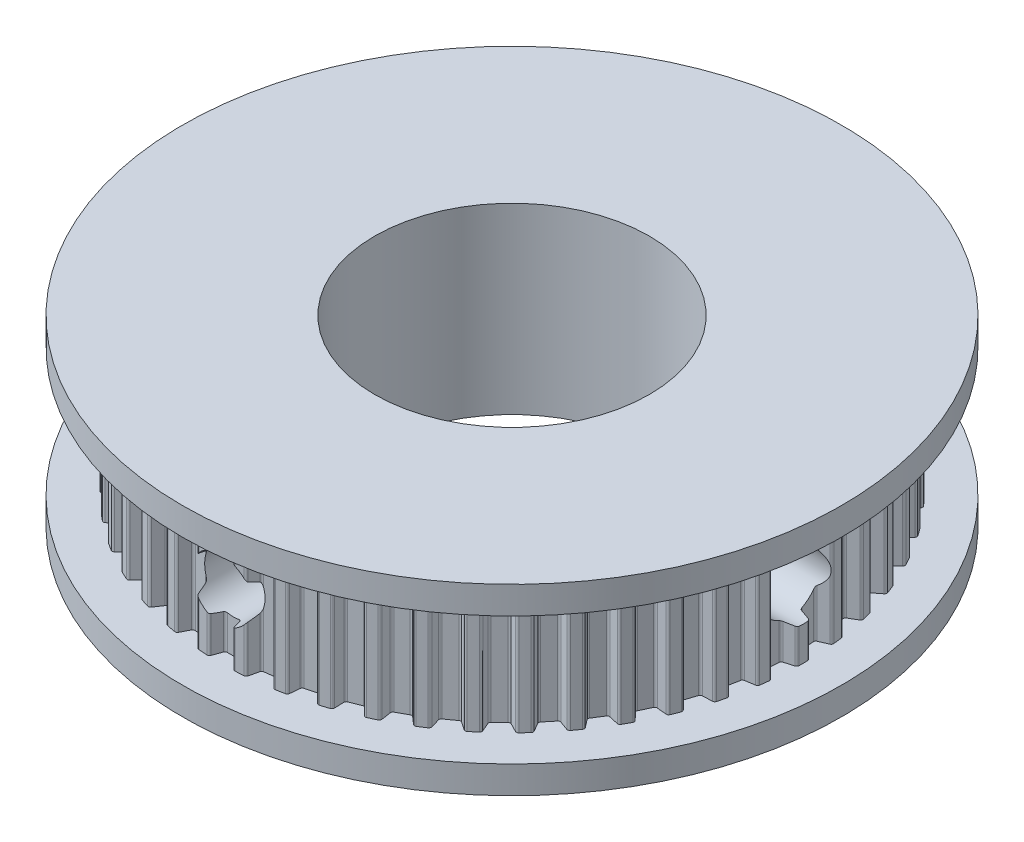
SolidWorks part; units mm, degrees
ref_plane "Front Plane" through (0, 0, 0) normal (0, 0, 1) x (1, 0, 0)
ref_plane "Top Plane" through (0, 0, 0) normal (0, 1, 0) x (1, 0, 0)
ref_plane "Right Plane" through (0, 0, 0) normal (1, 0, 0) x (0, 0, -1)
sketch "草圖1" plane through (0, 0, 0) normal (0, 1, 0) x (1, 0, 0)
  circle A0 centre (0, 0) radius 15.915
  dimension "D1" = 31.83
extrude "填料-伸長1" add sketch "草圖1" along normal blind 3.5 and the other way blind 3.5 contours A0
sketch "草圖2" plane through (0, -3.5, 0) normal (0, -1, 0) x (1, 0, 0)
  line L0 (0, 15.915) -> (0, 0) construction
  line L1 (0, 15.225) -> (-0.42, 15.225)
  line L2 (-0.42, 15.225) -> (-0.6661, 15.9011)
  line L3 (0, 15.225) -> (0.42, 15.225)
  line L4 (0.42, 15.225) -> (0.6661, 15.9011)
  circle A0 centre (0, 0) radius 15.915 construction
  arc A1 (-0.6661, 15.9011) -> (0.6661, 15.9011) centre (0, 0) cw
  circle M7 centre (0, 0) radius 15.915
  dimension "D1" = 0.69
  dimension "D2" = 0.84
  dimension "D3" = 40
extrude "除料-伸長1" cut sketch "草圖2" against normal through all contours L0 A1 L2 L1 | L0 L3 L4 M7 region at (0.2757, -3.5, 15.5938) region at (-0.2757, -3.5, 15.5938)
fillet "圓角1" radius 0.13 4 edges at (-0.6661, 0, 15.9011) (0.6661, 0, 15.9011) (0.42, 0, 15.225) (-0.42, 0, 15.225)
pattern_circular "環狀複製排列1" count 50 over 360 about axis through (0, -3.5, 0) along (0, 1, 0) of "圓角1", "除料-伸長1"
sketch "草圖3" plane through (0, 3.5, 0) normal (0, 1, 0) x (1, 0, 0)
  circle A0 centre (0, 0) radius 18
  dimension "D1" = 36
extrude "填料-伸長2" add sketch "草圖3" along normal blind 1.5
sketch "草圖4" plane through (0, -3.5, 0) normal (0, -1, 0) x (1, 0, 0)
  circle A0 centre (0, 0) radius 18
  circle A1 centre (0, 0) radius 18 construction
extrude "填料-伸長3" add sketch "草圖4" along normal blind 1.5
sketch "草圖5" plane through (0, -5, 0) normal (0, -1, 0) x (1, 0, 0)
  circle A0 centre (0, 0) radius 7.5
  dimension "D1" = 15
extrude "除料-伸長2" cut sketch "草圖5" against normal through all
hole_wizard "M4x0.7 螺紋孔1" positions "草圖8" profile "草圖9" tap size "M4x0.7" standard "Ansi Metric" end condition through all
sketch "草圖8" plane through (0, 0, 0) normal (0, 0, 1) x (1, 0, 0)
  point P0 (0, 0)
sketch "草圖9" plane through (0, 0, 0) normal (1, 0, 0) x (0, 1, 0)
  line L0 (0, 0) -> (0, 18)
  line L1 (0, 18) -> (1.65, 18)
  line L2 (1.65, 18) -> (1.65, 0)
  line L5 (1.65, 0) -> (0, 0)
  line L11 (0, -6.35) -> (0, 107.95) construction
  dimension "貫穿螺孔鑽直徑" = 3.3
  dimension "貫穿螺孔鑽深度" = 18
pattern_circular "環狀複製排列2" count 2 over 90 about axis through (0, 5, 0) along (0, -1, 0) of "M4x0.7 螺紋孔1" reverse direction yes
